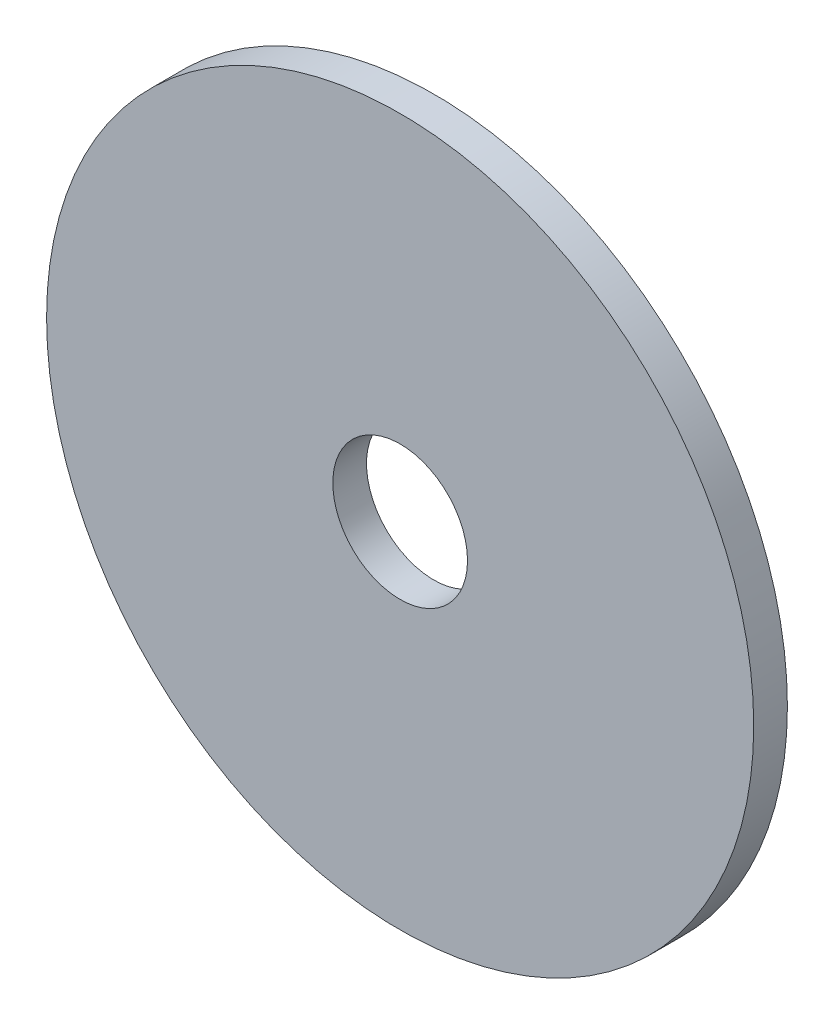
SolidWorks part; units mm, degrees
ref_plane "Front Plane" through (0, 0, 0) normal (0, 0, 1) x (1, 0, 0)
ref_plane "Top Plane" through (0, 0, 0) normal (0, 1, 0) x (1, 0, 0)
ref_plane "Right Plane" through (0, 0, 0) normal (1, 0, 0) x (0, 0, -1)
sketch "Sketch1" plane through (0, 0, 0) normal (0, 0, 1) x (1, 0, 0)
  circle A0 centre (0, 0) radius 52.5
  circle A1 centre (0, 0) radius 47.5
  circle A2 centre (0, 0) radius 10
  dimension "D1" = 105
  dimension "D2" = 95
  dimension "D3" = 20
extrude "Boss-Extrude2" add sketch "Sketch1" against normal blind 5 contours A1 A2 | A0 A1 region at (-51.0151, 0, 0) region at (-46.1565, 0, 0)
